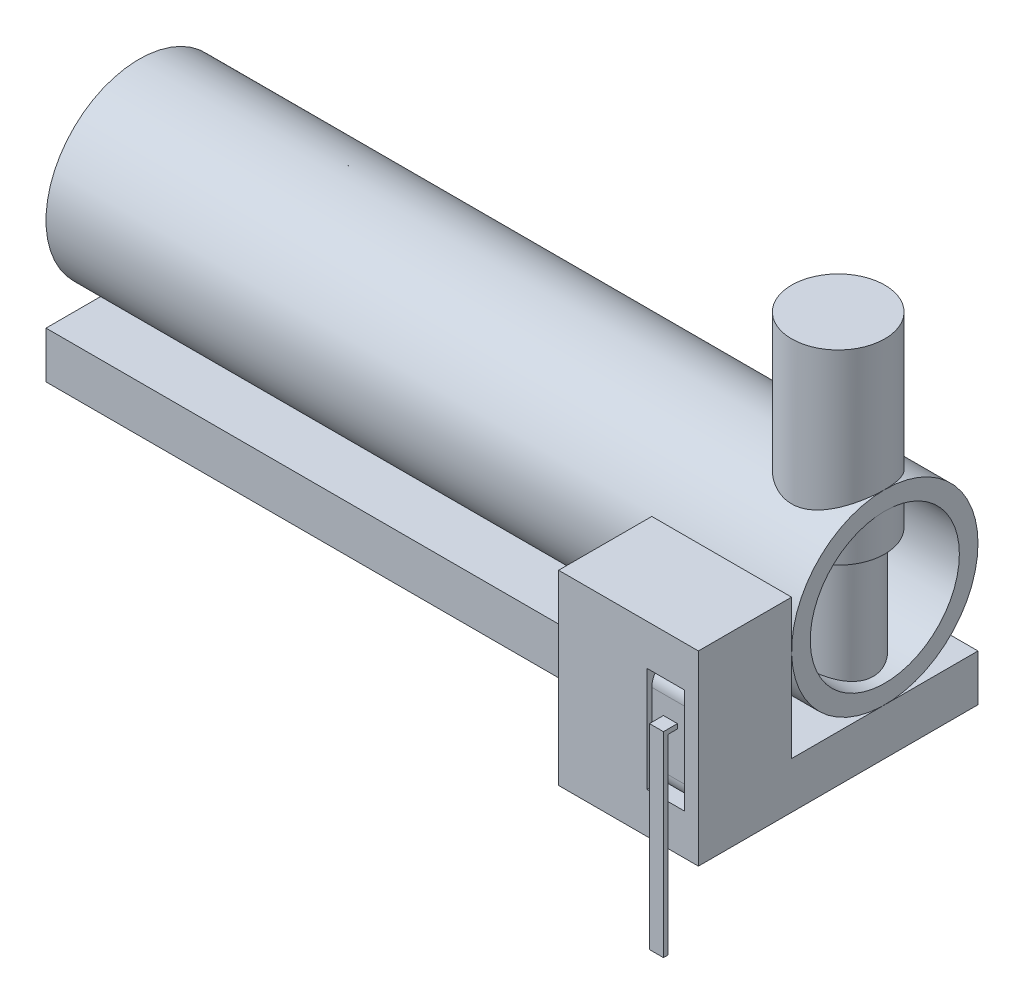
SolidWorks part; units mm, degrees
ref_plane "Front Plane" through (0, 0, 0) normal (0, 0, 1) x (1, 0, 0)
ref_plane "Top Plane" through (0, 0, 0) normal (0, 1, 0) x (1, 0, 0)
ref_plane "Right Plane" through (0, 0, 0) normal (1, 0, 0) x (0, 0, -1)
sketch "Sketch2" plane through (0, 0, 0) normal (1, 0, 0) x (0, 0, -1)
  line L0 (-25.4, 25.4) -> (-25.4, -25.4) construction
  line L1 (-25.4, -25.4) -> (25.4, -25.4) construction
  line L2 (25.4, -25.4) -> (25.4, 25.4) construction
  line L3 (25.4, 25.4) -> (-25.4, 25.4) construction
  point P2 (25.4, 0)
  point P5 (0, 25.4)
  dimension "D1" = 50.8
ref_plane "Plane1" through (0, 0, 0) normal (1, 0, 0) x (0, 0, -1)
sketch "Sketch3" plane through (0, 0, 0) normal (1, 0, 0) x (0, 0, -1)
  circle A0 centre (0, 0) radius 25.4
  dimension "D1" = 50.8
extrude "Boss-Extrude1" add sketch "Sketch3" against normal blind 203.2
shell "Shell1" thickness 5.08 removed face at (0, 0, -25.4)
sketch "Sketch4" plane through (0, 0, 0) normal (0, 0, 1) x (1, 0, 0)
  line L0 (-203.2, -25.4) -> (0, -25.4)
  line L2 (0, -27.94) -> (0, 27.94) construction
  line L3 (-203.2, -25.4) -> (0, -25.4) construction
  line L4 (-203.2, -25.4) -> (-203.2, -38.1)
  line L5 (-203.2, -38.1) -> (0, -38.1)
  line L6 (0, -38.1) -> (0, -25.4)
  dimension "D1" = 12.7
extrude "Boss-Extrude2" add sketch "Sketch4" along normal blind 25.4 and the other way blind 25.4 separate body
sketch "Sketch5" plane through (0, 0, 25.4) normal (0, 0, 1) x (1, 0, 0)
  line L1 (0, -38.1) -> (-38.1, -38.1)
  line L2 (0, -38.1) -> (0, 12.7)
  line L3 (0, 12.7) -> (-38.1, 12.7)
  line L4 (-38.1, -38.1) -> (-38.1, 12.7)
  line L8 (-203.2, -38.1) -> (0, -38.1) construction
  line L9 (0, -38.1) -> (0, -25.4) construction
  dimension "D1" = 38.1
  dimension "D2" = 50.8
extrude "Boss-Extrude3" add sketch "Sketch5" along normal blind 25.4
sketch "Sketch6" plane through (0, 0, 50.8) normal (0, 0, 1) x (1, 0, 0)
  line L1 (-3.81, -26.9875) -> (-13.97, -26.9875)
  line L2 (-3.81, -26.9875) -> (-3.81, 1.5875)
  line L3 (-3.81, 1.5875) -> (-13.97, 1.5875)
  line L4 (-13.97, -26.9875) -> (-13.97, 1.5875)
  line L5 (-3.81, 1.5875) -> (-3.81, 12.7) construction
  line L6 (0, 12.7) -> (-38.1, 12.7) construction
  line L7 (0, -38.1) -> (0, 12.7) construction
  line L8 (-3.81, -26.9875) -> (-3.81, -38.1) construction
  line L9 (-38.1, -38.1) -> (0, -38.1) construction
  dimension "D1" = 28.575
  dimension "D2" = 10.16
  dimension "D3" = 3.81
extrude "Cut-Extrude1" cut sketch "Sketch6" against normal blind 19.05
sketch "Sketch7" plane through (-13.97, 0, 0) normal (1, 0, 0) x (0, 0, -1)
  line L0 (-31.75, 1.5875) -> (-31.75, -26.9875) construction
  line L1 (-44.45, -26.9875) -> (-36.83, -26.9875)
  line L2 (-49.53, -21.9075) -> (-49.53, -3.4925)
  line L3 (-44.45, 1.5875) -> (-36.83, 1.5875)
  line L4 (-31.75, -21.9075) -> (-31.75, -3.4925)
  line L5 (-31.75, 1.5875) -> (-50.8, 1.5875) construction
  line L6 (-50.8, 1.5875) -> (-50.8, -26.9875) construction
  line L7 (-31.75, -26.9875) -> (-50.8, -26.9875) construction
  arc A0 (-36.83, -26.9875) -> (-31.75, -21.9075) centre (-36.83, -21.9075) ccw
  arc A1 (-44.45, -26.9875) -> (-49.53, -21.9075) centre (-44.45, -21.9075) cw
  arc A2 (-36.83, 1.5875) -> (-31.75, -3.4925) centre (-36.83, -3.4925) cw
  arc A3 (-49.53, -3.4925) -> (-44.45, 1.5875) centre (-44.45, -3.4925) cw
  point P14 (-50.8, -26.9875)
  dimension "D1" = 5.08
  dimension "D2" = 1.27
extrude "Boss-Extrude4" add sketch "Sketch7" along normal up to next
sketch "Sketch8" plane through (0, 0, 49.53) normal (0, 0, 1) x (1, 0, 0)
  line L0 (-3.81, -3.4925) -> (-13.97, -3.4925) construction
  line L1 (-10.795, -8.5725) -> (-6.985, -8.5725)
  line L2 (-10.795, -8.5725) -> (-10.795, -9.8425)
  line L3 (-10.795, -9.8425) -> (-6.985, -9.8425)
  line L4 (-6.985, -8.5725) -> (-6.985, -9.8425)
  point P6 (-8.89, -8.5725)
  point P7 (-8.89, -3.4925)
  dimension "D1" = 5.08
  dimension "D2" = 1.27
  dimension "D3" = 3.81
extrude "Boss-Extrude5" add sketch "Sketch8" along normal blind 2.54
sketch "Sketch10" plane through (0, 0, 52.07) normal (0, 0, 1) x (1, 0, 0)
  line L0 (-3.81, 1.5875) -> (-13.97, 1.5875) construction
  line L1 (-10.795, -8.5725) -> (-6.985, -8.5725)
  line L2 (-10.795, -8.5725) -> (-10.795, -61.9125)
  line L3 (-10.795, -61.9125) -> (-6.985, -61.9125)
  line L4 (-6.985, -8.5725) -> (-6.985, -61.9125)
  line L5 (-6.985, -9.8425) -> (-6.985, -8.5725) construction
  dimension "D1" = 63.5
extrude "Boss-Extrude6" add sketch "Sketch10" along normal blind 1.27
sketch "Sketch11" plane through (0, 0, 0) normal (0, 1, 0) x (1, 0, 0)
  circle A0 centre (-12.7, 0) radius 9.525
  dimension "D1" = 19.05
  dimension "D2" = 12.7
extrude "Boss-Extrude7" add sketch "Sketch11" along normal blind 10.16 and the other way up to next
sketch "Sketch12" plane through (0, 10.16, 0) normal (0, 1, 0) x (1, 0, 0)
  circle A0 centre (-12.7, 0) radius 12.7
extrude "Boss-Extrude8" add sketch "Sketch12" along normal blind 50.8 contours A0
